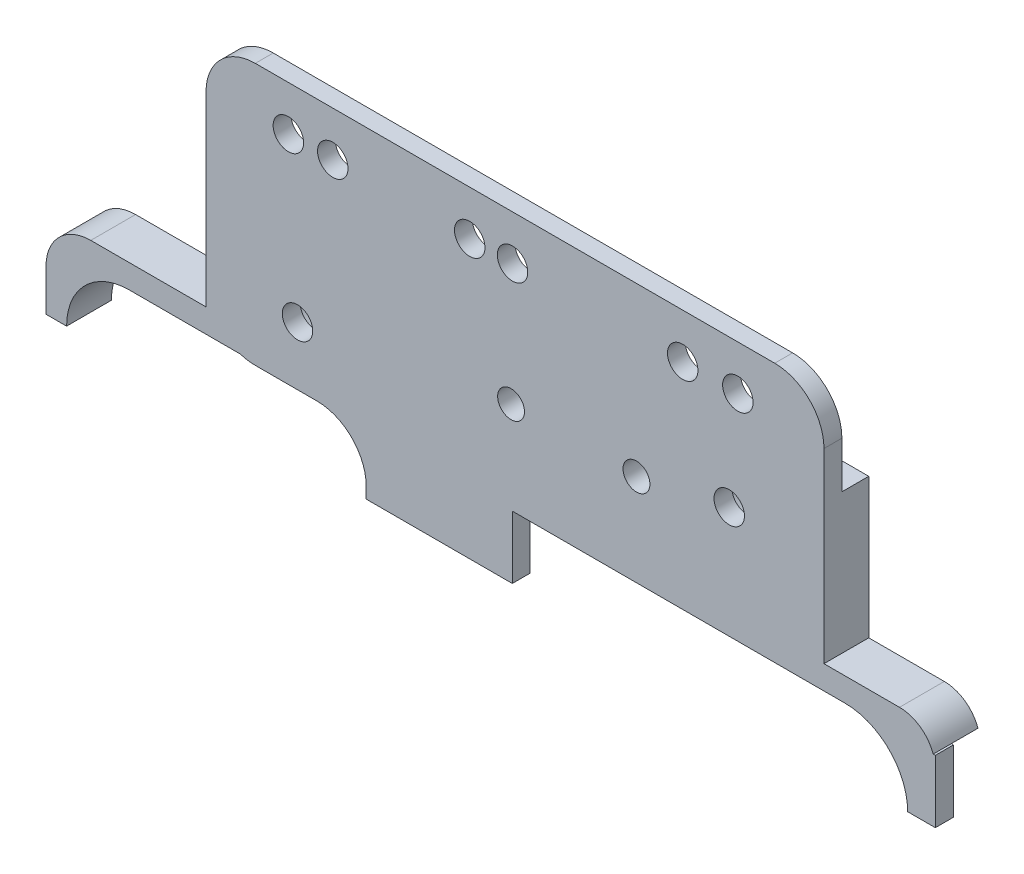
SolidWorks part; units mm, degrees
ref_plane "Plan de face" through (0, 0, 0) normal (0, 0, 1) x (1, 0, 0)
ref_plane "Plan de dessus" through (0, 0, 0) normal (0, 1, 0) x (1, 0, 0)
ref_plane "Plan de droite" through (0, 0, 0) normal (1, 0, 0) x (0, 0, -1)
sketch "Esquisse1" plane through (0, 0, 0) normal (0, 0, 1) x (1, 0, 0)
  line L0 (-101.8864, 22.7193) -> (-64.9263, 22.7193) construction
  line L1 (-68.0864, 83.4017) -> (-68.0864, 71.4017) construction
  line L2 (-118.8906, -27.2807) -> (-47.3665, -27.2807) construction
  line L3 (-120.7144, 72.7193) -> (-45.5428, 72.7193) construction
  line L4 (-83.4864, -42.5983) -> (-83.4864, 89.4017) construction
  line L5 (-56.8564, -27.2807) -> (-56.8564, 72.7193) construction
  line L6 (-110.1164, -27.2807) -> (-110.1164, 72.7193) construction
  line L7 (-59.2664, -27.2807) -> (-59.2664, 72.7193) construction
  line L8 (-56.8564, -13.2807) -> (-110.1164, -13.2807) construction
  line L9 (-64.3564, -27.2807) -> (-64.3564, 72.7193) construction
  line L10 (-110.1164, 36.7193) -> (-56.8564, 36.7193) construction
  line L11 (-56.8564, 66.9393) -> (-110.1164, 66.9393) construction
  line L12 (-91.8564, -27.2807) -> (-91.8564, 72.7193) construction
  line L13 (-107.4664, -27.2807) -> (-107.4664, 72.7193) construction
  line L14 (-56.8564, -14.5207) -> (-110.1164, -14.5207) construction
  line L15 (-110.1164, 60.7193) -> (-56.8564, 60.7193) construction
  line L16 (-117.6801, 66.9393) -> (-117.6801, 59.6951)
  line L17 (-112.1801, 54.1951) -> (-105.2942, 54.1951)
  line L18 (-99.7942, 48.6951) -> (-99.7942, 35.9308)
  line L19 (-112.1801, 83.4017) -> (-54.1904, 83.4017)
  line L20 (-105.2942, -3.8078) -> (-113.3906, -3.8078)
  line L21 (-118.8906, -9.3078) -> (-118.8906, -18.422)
  line L22 (-113.3906, -23.922) -> (-52.8665, -23.922)
  line L23 (-47.3665, -18.422) -> (-47.3665, -9.3078)
  line L24 (-52.8665, -3.8078) -> (-77.9864, -3.8078)
  line L25 (-83.4864, 1.6922) -> (-83.4864, 12.91)
  line L26 (-77.9864, 60.7193) -> (-54.1904, 60.7193)
  line L27 (-48.6904, 66.2193) -> (-48.6904, 67.2193)
  line L29 (-117.6801, 67.2193) -> (-117.6801, 66.9393)
  line L30 (-105.2942, 30.4308) -> (-112.1801, 30.4308)
  line L31 (-117.6801, 24.9308) -> (-117.6801, 23.91)
  line L32 (-112.1801, 18.41) -> (-105.2942, 18.41)
  line L33 (-77.9864, 30.4308) -> (-69.8564, 30.4308)
  line L34 (-64.3564, 24.9308) -> (-64.3564, 23.91)
  line L35 (-69.8564, 18.41) -> (-77.9864, 18.41)
  line L36 (-99.7942, 12.91) -> (-99.7942, 1.6922)
  line L37 (-111.3906, 21.4601) -> (-70.0864, 21.4601)
  line L38 (-113.3906, 23.4601) -> (-113.3906, 24.8425)
  line L39 (-111.3906, 26.8425) -> (-70.0864, 26.8425)
  line L40 (-68.0864, 23.4601) -> (-68.0864, 24.8425)
  line L41 (-83.4864, 35.9308) -> (-83.4864, 55.2193)
  line L42 (-117.6801, 67.2193) -> (-117.6801, 77.9017)
  line L43 (-48.6904, 67.2193) -> (-48.6904, 77.9017)
  circle A0 centre (-59.2664, -15.6637) radius 1.7
  arc A1 (-77.9864, 30.4308) -> (-83.4864, 35.9308) centre (-77.9864, 35.9308) cw
  circle A2 centre (-59.2664, 66.9393) radius 1.7
  circle A3 centre (-91.8564, 36.7193) radius 1.7
  arc A4 (-64.3564, 23.91) -> (-69.8564, 18.41) centre (-69.8564, 23.91) cw
  circle A6 centre (-107.4664, -14.5207) radius 1.7
  circle A7 centre (-107.4664, 60.7193) radius 1.7
  arc A8 (-117.6801, 59.6951) -> (-112.1801, 54.1951) centre (-112.1801, 59.6951) ccw
  arc A9 (-105.2942, 54.1951) -> (-99.7942, 48.6951) centre (-105.2942, 48.6951) cw
  arc A10 (-99.7942, 1.6922) -> (-105.2942, -3.8078) centre (-105.2942, 1.6922) cw
  arc A11 (-113.3906, -3.8078) -> (-118.8906, -9.3078) centre (-113.3906, -9.3078) ccw
  arc A12 (-118.8906, -18.422) -> (-113.3906, -23.922) centre (-113.3906, -18.422) ccw
  arc A13 (-52.8665, -23.922) -> (-47.3665, -18.422) centre (-52.8665, -18.422) ccw
  arc A14 (-47.3665, -9.3078) -> (-52.8665, -3.8078) centre (-52.8665, -9.3078) ccw
  arc A15 (-77.9864, -3.8078) -> (-83.4864, 1.6922) centre (-77.9864, 1.6922) cw
  arc A16 (-83.4864, 55.2193) -> (-77.9864, 60.7193) centre (-77.9864, 55.2193) cw
  arc A17 (-54.1904, 60.7193) -> (-48.6904, 66.2193) centre (-54.1904, 66.2193) ccw
  arc A19 (-69.8564, 30.4308) -> (-64.3564, 24.9308) centre (-69.8564, 24.9308) cw
  arc A20 (-77.9864, 18.41) -> (-83.4864, 12.91) centre (-77.9864, 12.91) ccw
  arc A21 (-105.2942, 18.41) -> (-99.7942, 12.91) centre (-105.2942, 12.91) cw
  arc A22 (-117.6801, 23.91) -> (-112.1801, 18.41) centre (-112.1801, 23.91) ccw
  arc A23 (-112.1801, 30.4308) -> (-117.6801, 24.9308) centre (-112.1801, 24.9308) ccw
  arc A24 (-105.2942, 30.4308) -> (-99.7942, 35.9308) centre (-105.2942, 35.9308) ccw
  arc A25 (-70.0864, 26.8425) -> (-68.0864, 24.8425) centre (-70.0864, 24.8425) cw
  arc A26 (-70.0864, 21.4601) -> (-68.0864, 23.4601) centre (-70.0864, 23.4601) ccw
  arc A27 (-111.3906, 21.4601) -> (-113.3906, 23.4601) centre (-111.3906, 23.4601) cw
  arc A28 (-113.3906, 24.8425) -> (-111.3906, 26.8425) centre (-111.3906, 24.8425) cw
  circle A29 centre (-58.3064, 78.3993) radius 1.7
  circle A30 centre (-108.4864, 78.3993) radius 1.7
  arc A31 (-48.6904, 77.9017) -> (-54.1904, 83.4017) centre (-54.1904, 77.9017) ccw
  arc A32 (-117.6801, 77.9017) -> (-112.1801, 83.4017) centre (-112.1801, 77.9017) cw
  point P61 (-117.6801, 72.7193)
  point P68 (-99.7942, -3.8078)
  point P79 (-83.4864, -3.8078)
  point P82 (-83.4864, 60.7193)
  point P87 (-48.6904, 72.7193)
  point P98 (-83.4864, 30.4308)
  point P101 (-64.3564, 18.41)
  point P104 (-64.3564, 30.4308)
  point P109 (-99.7942, 18.41)
  point P116 (-99.7942, 30.4308)
  dimension "D2" = 5.5
  dimension "D3" = 2
  dimension "D6" = 1.02
  dimension "D8" = 5.5
  dimension "D4" = 0.96
  dimension "D5" = 11.46
  dimension "D7" = 17.68
extrude "Boss.-Extru.1" add sketch "Esquisse1" along normal blind 3
sketch "Esquisse2" plane through (0, 0, 0) normal (0, 0, -1) x (-1, 0, 0)
  line L0 (39.3464, 87.1044) -> (39.3464, -42.3137) construction
  line L1 (133.2464, 87.1044) -> (133.2464, 37.9772) construction
  line L2 (59.2664, -15.6637) -> (59.2664, 1.7249) construction
  line L3 (133.2464, -8.2937) -> (39.3464, -8.2937) construction
  line L4 (133.2464, 54.4563) -> (39.3464, 54.4563) construction
  line L5 (126.2464, -8.2937) -> (126.2464, -1.2937) construction
  line L6 (126.2464, -1.2937) -> (133.2464, -1.2937) construction
  line L7 (126.2464, 54.4563) -> (126.2464, 47.4563) construction
  line L8 (126.2464, 47.4563) -> (133.2464, 47.4563) construction
  line L9 (46.3464, 54.4563) -> (46.3464, 47.4563) construction
  line L10 (46.3464, 47.4563) -> (39.3464, 47.4563) construction
  line L11 (39.3464, -1.2937) -> (46.3464, -1.2937) construction
  line L12 (46.3464, -1.2937) -> (46.3464, -8.2937) construction
  line L13 (118.8906, -9.9695) -> (130.5846, -9.8801)
  line L14 (117.6801, 57.0999) -> (130.5464, 57.0999)
  line L15 (47.3665, -10.5841) -> (47.3665, -23.922)
  line L16 (36.2569, 53.0999) -> (36.2569, 47.4563)
  line L17 (36.2569, 47.4563) -> (39.3464, 47.4563)
  line L18 (39.3464, -1.2937) -> (36.2482, -1.2937)
  line L19 (36.2482, -1.2937) -> (36.2482, -6.6454)
  line L20 (40.2828, -10.6453) -> (47.3665, -10.5841)
  line L21 (48.6904, 60.7193) -> (48.6904, 72.7193)
  line L22 (48.6904, 60.7193) -> (48.6904, 57.0999)
  line L23 (126.2464, 54.4563) -> (46.3464, 54.4563)
  line L24 (46.3464, -8.2937) -> (126.2464, -8.2937)
  line L25 (133.2464, 47.4563) -> (133.2464, 40.9772)
  line L26 (48.6904, 72.7193) -> (117.6801, 72.7193)
  line L27 (138.5464, 8.4156) -> (145.7527, 8.4156)
  line L28 (40.2569, 57.0999) -> (48.6904, 57.0999)
  line L29 (148.7527, 11.4156) -> (148.7527, 38.1792)
  line L30 (133.2464, 34.4495) -> (133.2464, -42.3137) construction
  line L32 (117.6801, 72.7193) -> (117.6801, 57.0999)
  line L35 (135.5464, -24.0475) -> (135.5464, 64.4693) construction
  line L36 (47.3665, -18.422) -> (47.3665, -9.3078) construction
  line L37 (133.2464, 8.3631) -> (133.2464, -1.2937)
  line L38 (47.3665, -23.922) -> (118.8906, -23.922)
  line L39 (118.8906, -23.922) -> (118.8906, -9.9695)
  line L40 (118.8906, -9.3078) -> (118.8906, -18.422) construction
  line L41 (145.7527, 41.1792) -> (138.5464, 41.1792)
  line L42 (136.2464, 11.3631) -> (142.1623, 11.3631)
  line L43 (145.1623, 14.3631) -> (145.1623, 34.9772)
  line L44 (142.1623, 37.9772) -> (136.2464, 37.9772)
  line L47 (135.5464, -4.8802) -> (135.5464, 5.4156)
  line L57 (135.5464, 44.1792) -> (135.5464, 52.0999)
  arc A0 (133.2464, -1.2937) -> (126.2464, -8.2937) centre (126.2464, -1.2937) cw
  arc A1 (133.2464, 47.4563) -> (126.2464, 54.4563) centre (126.2464, 47.4563) ccw
  arc A2 (46.3464, 54.4563) -> (39.3464, 47.4563) centre (46.3464, 47.4563) ccw
  arc A3 (39.3464, -1.2937) -> (46.3464, -8.2937) centre (46.3464, -1.2937) ccw
  arc A4 (40.2569, 57.0999) -> (36.2569, 53.0999) centre (40.2569, 53.0999) ccw
  arc A5 (148.7527, 38.1792) -> (145.7527, 41.1792) centre (145.7527, 38.1792) ccw
  arc A6 (138.5464, 41.1792) -> (135.5464, 44.1792) centre (138.5464, 44.1792) cw
  arc A7 (136.2464, 37.9772) -> (133.2464, 40.9772) centre (136.2464, 40.9772) cw
  arc A8 (145.1623, 34.9772) -> (142.1623, 37.9772) centre (142.1623, 34.9772) ccw
  arc A9 (142.1623, 11.3631) -> (145.1623, 14.3631) centre (142.1623, 14.3631) ccw
  arc A10 (145.7527, 8.4156) -> (148.7527, 11.4156) centre (145.7527, 11.4156) ccw
  arc A11 (133.2464, 8.3631) -> (136.2464, 11.3631) centre (136.2464, 8.3631) cw
  arc A12 (135.5464, 52.0999) -> (130.5464, 57.0999) centre (130.5464, 52.0999) ccw
  arc A13 (138.5464, 8.4156) -> (135.5464, 5.4156) centre (138.5464, 5.4156) ccw
  arc A15 (130.5846, -9.8801) -> (135.5464, -4.8802) centre (130.5464, -4.8802) ccw
  arc A16 (36.2482, -6.6454) -> (40.2828, -10.6453) centre (40.2482, -6.6454) ccw
  circle A17 centre (59.2664, -15.6637) radius 5.2
  circle A18 centre (107.4664, -14.5207) radius 5.2
  circle A19 centre (107.4664, 60.7193) radius 5.2
  circle A20 centre (59.2664, 66.9393) radius 5.2
  point P34 (135.5464, 57.0999)
  point P37 (132.9964, 22.9063)
  point P43 (132.9964, 22.9063)
  point P45 (133.2464, 29.4495)
  point P50 (133.2464, 16.3631)
  point P62 (111.5444, -10.0296)
  point P71 (64.0892, -10.4396)
  point P74 (135.5464, 26.097)
  point P75 (134.7715, 19.7156)
  point P107 (135.5464, 19.7156)
  point P110 (135.5464, -9.8421)
  dimension "D13" = 4
  dimension "D14" = 3
  dimension "D16" = 5
  dimension "D1" = 19.92
  dimension "D2" = 93.9
  dimension "D3" = 7.37
  dimension "D4" = 62.75
  dimension "D5" = 7
  dimension "D6" = 7
  dimension "D7" = 7
  dimension "D8" = 7
  dimension "D9" = 7
  dimension "D10" = 7
  dimension "D11" = 7
  dimension "D12" = 7
  dimension "D17" = 2.3
extrude "Boss.-Extru.2" add sketch "Esquisse2" along normal blind 3 and the other way blind 3
sketch "Esquisse5" plane through (0, 0, 3) normal (0, 0, 1) x (1, 0, 0)
  line L1 (-156.3908, -30.1977) -> (-27.0007, -30.1977)
  line L2 (-156.3908, -30.1977) -> (-156.3908, 89.8557)
  line L3 (-156.3908, 89.8557) -> (-27.0007, 89.8557)
  line L4 (-27.0007, -30.1977) -> (-27.0007, 89.8557)
extrude "Enlèv. mat.-Extru.2" cut sketch "Esquisse5" against normal blind 1
sketch "Esquisse6" plane through (0, 0, 2) normal (0, 0, 1) x (1, 0, 0)
  line L0 (-69.6235, 64.7274) -> (-83.6235, 64.7274) construction
  circle A0 centre (-69.6235, 64.7274) radius 1.5
  circle A1 centre (-83.6235, 64.7274) radius 1.5
extrude "Enlèv. mat.-Extru.3" cut sketch "Esquisse6" against normal blind 8
sketch "Esquisse7" plane through (0, 0, 0) normal (0, 0, -1) x (-1, 0, 0)
  line L0 (47.4608, -8.2937) -> (118.7963, -8.2937) construction
  line L1 (49.8731, -8.2937) -> (35.2624, -8.2937)
  line L2 (49.8731, -8.2937) -> (49.8731, 54.4563)
  line L3 (49.8731, 54.4563) -> (35.2624, 54.4563)
  line L4 (35.2624, -8.2937) -> (35.2624, 54.4563)
  line L5 (113.8548, 54.4563) -> (83.4864, 54.4563) construction
extrude "Enlèv. mat.-Extru.4" cut sketch "Esquisse7" along normal blind 8
sketch "Esquisse9" plane through (0, -1.2937, 0) normal (0, 1, 0) x (1, 0, 0)
  line L0 (-39.3464, -2) -> (-39.3464, 0.886)
  line L1 (-39.3464, 0.886) -> (-36.2482, 0)
  line L2 (-36.2482, 0) -> (-36.2482, -2)
  line L3 (-36.2482, -2) -> (-39.3464, -2)
extrude "Boss.-Extru.3" add sketch "Esquisse9" against normal blind 7
sketch "Esquisse10" plane through (0, 47.4563, 0) normal (0, -1, 0) x (1, 0, 0)
  line L0 (-39.3464, 2) -> (-39.3464, -0.873)
  line L1 (-39.3464, -0.873) -> (-36.2569, 0)
  line L2 (-36.2569, 0) -> (-36.2569, 2)
  line L3 (-36.2569, 2) -> (-39.3464, 2)
extrude "Boss.-Extru.4" add sketch "Esquisse10" against normal blind 7
sketch "Esquisse11" plane through (0, 47.4563, 0) normal (0, -1, 0) x (1, 0, 0)
  line L1 (-18.3633, 6.1891) -> (-167.4147, 6.1891)
  line L2 (-18.3633, 6.1891) -> (-18.3633, -7.1775)
  line L3 (-18.3633, -7.1775) -> (-167.4147, -7.1775)
  line L4 (-167.4147, 6.1891) -> (-167.4147, -7.1775)
extrude "Enlèv. mat.-Extru.5" cut sketch "Esquisse11" along normal blind 80
sketch "Esquisse13" plane through (0, 0, 2) normal (0, 0, 1) x (1, 0, 0)
  line L0 (-108.4864, 78.3993) -> (-61.6094, 78.3993) construction
  circle A0 centre (-103.5291, 78.3993) radius 1.7
  circle A1 centre (-88.2391, 78.3993) radius 1.7
  circle A2 centre (-83.4621, 78.3993) radius 1.7
  circle A3 centre (-64.4621, 78.3993) radius 1.7
  dimension "D1" = 15.29
  dimension "D2" = 19
extrude "Enlèv. mat.-Extru.6" cut sketch "Esquisse13" against normal blind 15
